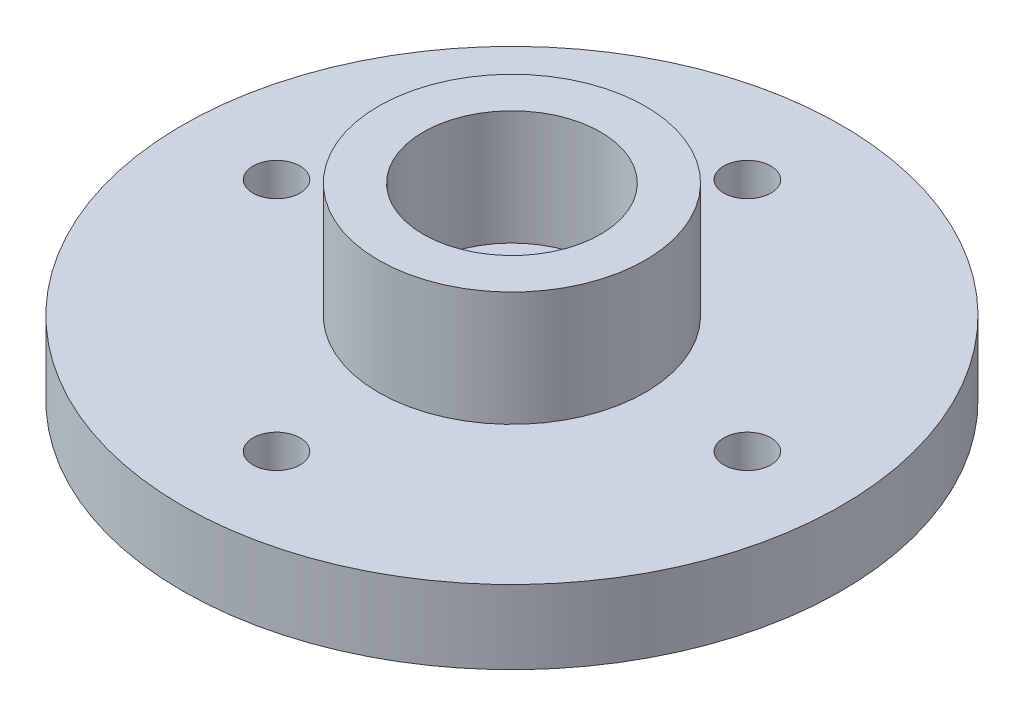
SolidWorks part; units mm, degrees
ref_plane "Front Plane" through (0, 0, 0) normal (0, 0, 1) x (1, 0, 0)
ref_plane "Top Plane" through (0, 0, 0) normal (0, 1, 0) x (1, 0, 0)
ref_plane "Right Plane" through (0, 0, 0) normal (1, 0, 0) x (0, 0, -1)
ref_axis "X" through (-88.99, 0, 0) along (1, 0, 0)
ref_axis "Y" through (0, 55, 0) along (0, -1, 0)
ref_axis "Z" through (0, 0, -88.99) along (0, 0, 1)
sketch "Sketch1" plane through (0, 0, 0) normal (0, 1, 0) x (1, 0, 0)
  line L0 (-7.5, 0) -> (0, 0) construction
  circle A0 centre (0, 0) radius 10.5
  circle A1 centre (0, 0) radius 4.25
  circle A2 centre (0, 0) radius 2.825
  circle A3 centre (-7.5, 0) radius 0.75
  circle A7 centre (0, 7.5) radius 0.75
  circle A8 centre (7.5, 0) radius 0.75
  circle A9 centre (0, -7.5) radius 0.75
  circle A10 centre (0, 0) radius 1.5
  point P16 (0, 0)
  dimension "D1" = 21
  dimension "D2" = 8.5
  dimension "D3" = 5.65
  dimension "D4" = 7.5
  dimension "D5" = 1.5
  dimension "D7" = 3
  dimension "D6" = 4
extrude "Boss-Extrude1" add sketch "Sketch1" along normal blind 2.35 contours A0 A9 A8 A7 A3 A1 | A1 A2 | A2 region at (-10.203, 0, 0) region at (-4.1298, 0, 0) region at (-2.7451, 0, 0)
extrude "Boss-Extrude2" add sketch "Sketch1<3>" along normal blind 3.65 from surface contours A1 A2 region at (-4.1298, 0, 0) starting at face at (0, 2.35, 8.25)
sketch "Sketch1<3>" plane through (0, 0, 0) normal (0, 1, 0) x (1, 0, 0) same geometry as "Sketch1"
